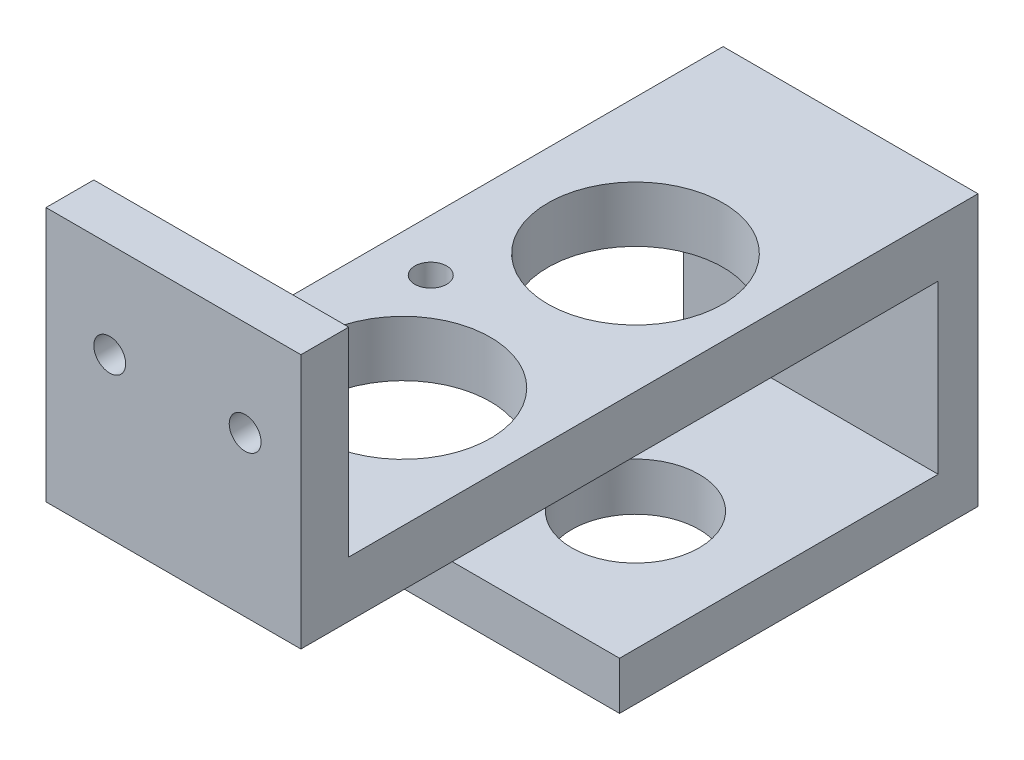
SolidWorks part; units mm, degrees
ref_plane "Front Plane" through (0, 0, 0) normal (0, 0, 1) x (1, 0, 0)
ref_plane "Top Plane" through (0, 0, 0) normal (0, 1, 0) x (1, 0, 0)
ref_plane "Right Plane" through (0, 0, 0) normal (1, 0, 0) x (0, 0, -1)
sketch "Sketch1" plane through (0, 0, 0) normal (0, 1, 0) x (1, 0, 0)
  line L1 (-50.1619, 28.7652) -> (-18.1619, 28.7652)
  line L2 (-50.1619, 28.7652) -> (-50.1619, -56.2348)
  line L3 (-50.1619, -56.2348) -> (-18.1619, -56.2348)
  line L4 (-18.1619, 28.7652) -> (-18.1619, -56.2348)
  dimension "D1" = 85
  dimension "D2" = 32
extrude "Boss-Extrude1" add sketch "Sketch1" along normal blind 7
sketch "Sketch2" plane through (0, 7, 0) normal (0, 1, 0) x (1, 0, 0)
  line L0 (-50.1619, -56.2348) -> (-18.1619, -56.2348) construction
  line L1 (-50.1619, 28.7652) -> (-50.1619, -56.2348) construction
  circle A0 centre (-33.1619, 0.7652) radius 11
  dimension "D1" = 22
  dimension "D2" = 57
  dimension "D3" = 17
extrude "Cut-Extrude1" cut sketch "Sketch2" against normal blind 100
sketch "Sketch3" plane through (0, 7, 0) normal (0, 1, 0) x (1, 0, 0)
  line L0 (-50.1619, 28.7652) -> (-50.1619, -56.2348) construction
  circle A0 centre (-33.1619, -28.4348) radius 11
  circle A1 centre (-33.1619, 0.7652) radius 11 construction
  dimension "D1" = 22
  dimension "D2" = 29.2
  dimension "D3" = 17
extrude "Cut-Extrude2" cut sketch "Sketch3" against normal blind 7
sketch "Sketch4" plane through (0, 7, 0) normal (0, 1, 0) x (1, 0, 0)
  line L0 (-18.1619, -56.2348) -> (-18.1619, 28.7652) construction
  line L1 (-50.1619, -56.2348) -> (-18.1619, -56.2348)
  line L2 (-50.1619, -56.2348) -> (-50.1619, -50.2348)
  line L3 (-50.1619, -50.2348) -> (-18.1619, -50.2348)
  line L4 (-18.1619, -56.2348) -> (-18.1619, -50.2348)
  dimension "D1" = 6
extrude "Boss-Extrude3" add sketch "Sketch4" along normal blind 25
sketch "Sketch5" plane through (0, 0, 50.2348) normal (0, 0, -1) x (-1, 0, 0)
  line L0 (50.1619, 32) -> (50.1619, 7) construction
  line L1 (18.1619, 32) -> (50.1619, 32) construction
  circle A0 centre (42.1619, 20) radius 2
  circle A1 centre (25.1619, 20) radius 2
  dimension "D1" = 4
  dimension "D2" = 4
  dimension "D3" = 8
  dimension "D4" = 17
  dimension "D5" = 0
  dimension "D6" = 12
extrude "Cut-Extrude3" cut sketch "Sketch5" against normal blind 14
sketch "Sketch6" plane through (0, 7, 0) normal (0, 1, 0) x (1, 0, 0)
  circle A0 centre (-43.6619, -14.4348) radius 2
  circle A1 centre (-43.6619, -42.4348) radius 2
  circle A2 centre (-33.1619, -28.4348) radius 11 construction
  dimension "D1" = 4
  dimension "D2" = 4
  dimension "D3" = 28
  dimension "D4" = 10.5
  dimension "D5" = 14
  dimension "D6" = 0
extrude "Cut-Extrude4" cut sketch "Sketch6" against normal blind 14
sketch "Sketch9" plane through (0, 7, 0) normal (0, 1, 0) x (1, 0, 0)
  circle A2 centre (-33.1619, 0.7652) radius 8
  circle A3 centre (-33.1619, 0.7652) radius 11 construction
  dimension "D1" = 16
  dimension "D2" = 0
sketch "Sketch10" plane through (0, 0, 0) normal (0, -1, 0) x (1, 0, 0)
  line L0 (-18.1619, 56.2348) -> (-18.1619, -28.7652) construction
  line L1 (-50.1619, -28.7652) -> (-18.1619, -28.7652)
  line L2 (-50.1619, -28.7652) -> (-50.1619, -23.7652)
  line L3 (-50.1619, -23.7652) -> (-18.1619, -23.7652)
  line L4 (-18.1619, -28.7652) -> (-18.1619, -23.7652)
  dimension "D1" = 5
extrude "Boss-Extrude4" add sketch "Sketch10" along normal blind 27
sketch "Sketch11" plane through (0, 0, -23.7652) normal (0, 0, 1) x (1, 0, 0)
  line L0 (-18.1619, -27) -> (-18.1619, 0) construction
  line L1 (-50.1619, -27) -> (-18.1619, -27)
  line L2 (-50.1619, -27) -> (-50.1619, -21)
  line L3 (-50.1619, -21) -> (-18.1619, -21)
  line L4 (-18.1619, -27) -> (-18.1619, -21)
  dimension "D1" = 6
extrude "Boss-Extrude5" add sketch "Sketch11" along normal blind 40
extrude "Cut-Extrude5" cut sketch "Sketch9" against normal blind 40
